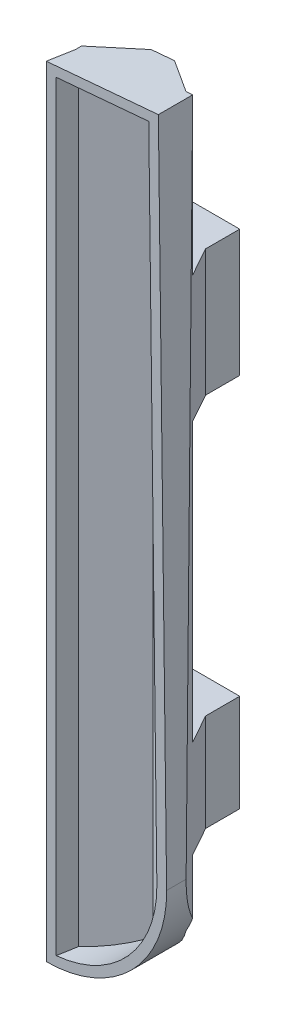
SolidWorks part; units mm, degrees
ref_plane "Front Plane" through (0, 0, 0) normal (0, 0, 1) x (1, 0, 0)
ref_plane "Top Plane" through (0, 0, 0) normal (0, 1, 0) x (1, 0, 0)
ref_plane "Right Plane" through (0, 0, 0) normal (1, 0, 0) x (0, 0, -1)
sketch "Sketch1" plane through (0, 0, 0) normal (0, 0, 1) x (1, 0, 0)
  line L0 (0, 0) -> (0, 160)
  line L1 (0, 160) -> (23, 162.0122)
  line L2 (23, 162.0122) -> (24.693, 25)
  line L3 (0, 0) -> (-10, 0) construction
  arc A0 (24.693, 25) -> (0, 0) centre (0, 24.6949) cw
  point P6 (24.0103, 50.0035)
  point P8 (24.6946, 162.8435)
  dimension "D1" = 25
  dimension "D2" = 10
  dimension "D3" = 23
  dimension "D4" = 160
  dimension "D5" = 95
extrude "Front shape block" add sketch "Sketch1" against normal blind 20
sketch "Sketch2" plane through (0, 0, 0) normal (0, 1, 0) x (1, 0, 0)
  line L0 (0, 0) -> (1, 5)
  line L1 (1, 5) -> (1, 20)
  line L2 (23, 20) -> (0, 20) construction
  line L3 (1, 20) -> (0, 20)
  line L4 (19.693, 13) -> (24.693, 4)
  line L5 (24.693, 20) -> (24.693, 0) construction
  line L6 (0, 20) -> (0, 0)
  line L8 (24.693, 20) -> (24.693, 4) construction
  line L9 (19.693, 13) -> (19.693, 20)
  line L10 (19.693, 20) -> (24.693, 20)
  line L11 (24.693, 20) -> (25.693, 20)
  line L12 (25.693, 20) -> (25.693, 4)
  line L13 (25.693, 4) -> (24.693, 4)
  dimension "D1" = 1
  dimension "D2" = 5
  dimension "D3" = 4
  dimension "D4" = 5
  dimension "D5" = 9
  dimension "D6" = 1
extrude "Vertical shape cut" cut sketch "Sketch2" along normal through all
sketch "Sketch3" plane through (0, 0, -20) normal (0, 0, -1) x (-1, 0, 0)
  line L0 (0, 160) -> (0, 0) construction
  line L1 (-23, 162.0122) -> (0, 162.0122)
  line L3 (-23.3954, 130.0122) -> (0, 130.0122)
  line L4 (0, 162.0122) -> (0, 130.0122)
  line L5 (-24.693, 25) -> (-23, 162.0122) construction
  line L6 (-23.3954, 130.0122) -> (-23, 162.0122)
  line L7 (-23.7167, 104.0122) -> (-24.421, 47.0122)
  line L8 (-24.421, 47.0122) -> (0, 47.0122)
  line L9 (0, 47.0122) -> (0, 104.0122)
  line L10 (0, 104.0122) -> (-23.7167, 104.0122)
  line L11 (0, 0) -> (0, 27.0122)
  line L12 (0, 27.0122) -> (-24.6681, 27.0122)
  line L13 (-24.6681, 27.0122) -> (-24.693, 25)
  arc A0 (-24.693, 25) -> (0, 0) centre (0, 24.6949) ccw construction
  arc A1 (-24.693, 25) -> (0, 0) centre (0, 24.6949) ccw
  dimension "D1" = 32
  dimension "D2" = 58
  dimension "D3" = 115
  dimension "D4" = 135
extrude "Internal tab clearance cut" cut sketch "Sketch3" against normal offset from surface (8 mm away) 12 up to face at (13.229, 85.4634, 0)
shell "Shell" thickness 2 removed face at (13.229, 85.4634, 0)
sketch "Sketch4" plane through (0, 0, -10) normal (0, 0, 1) x (1, 0, 0)
  line L0 (19.0717, 45.0122) -> (3, 45.0122)
  line L1 (3, 45.0122) -> (3, 29.0122)
  line L2 (3, 29.0122) -> (19.0717, 29.0122)
  line L3 (19.0717, 29.0122) -> (19.0717, 45.0122)
  line L4 (19.0717, 128.0122) -> (3, 128.0122)
  line L5 (3, 128.0122) -> (3, 106.0122)
  line L6 (3, 106.0122) -> (19.0717, 106.0122)
  line L7 (19.0717, 106.0122) -> (19.0717, 128.0122)
extrude "Mount tab fill" add sketch "Sketch4" against normal up to next
ref_plane "Plane1" through (0, 158.2548, 0) normal (0, 1, 0) x (1, 0, 0)
sketch "Sketch5" plane through (19.7814, 158.2548, 0) normal (0, 1, 0) x (-1, 0, 0)
  line L14 (16.9748, -3.8351) -> (7.8647, -10)
  line L15 (16.7814, -4.802) -> (17.7418, 0) construction
  line L16 (0.7097, -10) -> (16.7814, -10) construction
  line L17 (7.8647, -10) -> (-1.2454, -3.8351)
  line L18 (-1.2454, -6.4809) -> (-1.2454, 0) construction
  line L19 (-1.2454, -3.8351) -> (-1.2454, -6.4809)
  line L20 (-1.2454, -6.4809) -> (0.7097, -10)
  line L21 (0.7097, -10) -> (7.8647, -10)
  line L22 (16.7814, -10) -> (16.7814, -4.802)
  line L23 (16.7814, -4.802) -> (16.9748, -3.8351)
  line L24 (7.8647, -10) -> (16.7814, -10)
  point P16 (16.5963, -10)
  dimension "D1" = 11
extrude "LED strip tray" add sketch "Sketch5" against normal up to surface and the other way up to surface contours L20 L21 L17 L19 | L14 L24 L22 L23 region at (5.9631, 158.2548, -7.9773) region at (17.6571, 158.2548, -7.8219) up to face at (14.5201, 12.4524, -4.3202) other way up to face at (11.5275, 159.0009, -5.2138)
sketch "Sketch6" plane through (21.0268, 0, 0) normal (1, 0, 0) x (0, 0, -1)
  line L4 (3.8351, 159.832) -> (3.8351, 16.1549)
  line L5 (3.8351, 16.1549) -> (6.4809, 16.1549)
  line L6 (6.4809, 16.1549) -> (6.4809, 159.832)
  line L7 (6.4809, 159.832) -> (3.8351, 159.832)
  line L8 (3.8351, 159.832) -> (3.8351, 16.1549)
  line L9 (3.8351, 16.1549) -> (6.4809, 16.1549)
  line L10 (6.4809, 16.1549) -> (6.4809, 159.832)
  line L11 (6.4809, 159.832) -> (3.8351, 159.832)
  dimension "D1" = 0
extrude "Tray gap fill" add sketch "Sketch6" along normal up to next
sketch "Sketch7" plane through (0, 130.0122, 0) normal (0, 1, 0) x (1, 0, 0)
  line L0 (11.9167, 10) -> (21.0268, 3.8351) construction
  line L1 (2.8066, 3.8351) -> (11.9167, 10) construction
  line L2 (11.9167, 10) -> (21.0268, 3.8351) construction
  line L3 (2.8066, 3.8351) -> (11.9167, 10) construction
  line L4 (1, 6.2349) -> (9.5193, 12)
  line L7 (1, 12) -> (20.2486, 12) construction
  line L8 (1, 12) -> (1, 5) construction
  line L9 (14.3141, 12) -> (21.6327, 7.0474)
  line L10 (23, 7.0474) -> (21.6327, 7.0474)
  line L11 (23, 7.0474) -> (20.2486, 12)
  line L12 (20.2486, 12) -> (14.3141, 12)
  line L13 (9.5193, 12) -> (1, 12)
  line L14 (1, 12) -> (1, 6.2349)
  dimension "D1" = 3
  dimension "D2" = 3
extrude "Cut-Extrude4" cut sketch "Sketch7" along normal through all
sketch "Sketch8" plane through (0, 47.0122, 0) normal (0, 1, 0) x (1, 0, 0)
  line L3 (9.5193, 12) -> (1, 12)
  line L4 (14.3141, 12) -> (21.6327, 7.0474)
  line L5 (21.6327, 7.0474) -> (23, 7.0474)
  line L6 (23, 7.0474) -> (20.2486, 12)
  line L7 (20.2486, 12) -> (14.3141, 12)
  line L8 (14.3141, 12) -> (21.6327, 7.0474)
  line L9 (21.6327, 7.0474) -> (23, 7.0474)
  line L10 (23, 7.0474) -> (20.2486, 12)
  line L11 (20.2486, 12) -> (14.3141, 12)
  line L12 (1, 6.2349) -> (9.5193, 12)
  line L13 (1, 12) -> (1, 6.2349)
  line L14 (9.5193, 12) -> (1, 12)
  line L15 (1, 6.2349) -> (9.5193, 12)
  line L16 (1, 12) -> (1, 6.2349)
  dimension "D1" = 0
  dimension "D2" = 0
extrude "Cut-Extrude5" cut sketch "Sketch8" along normal up to surface (57 mm away) up to face at (12.3269, 104.0122, -15.4)
sketch "Sketch9" plane through (0, 27.0122, 0) normal (0, -1, 0) x (1, 0, 0)
  line L3 (1, -12) -> (9.5193, -12)
  line L4 (21.6327, -7.0474) -> (14.3141, -12)
  line L5 (23, -7.0474) -> (21.6327, -7.0474)
  line L6 (20.2486, -12) -> (23, -7.0474)
  line L7 (14.3141, -12) -> (20.2486, -12)
  line L8 (21.6327, -7.0474) -> (14.3141, -12)
  line L9 (23, -7.0474) -> (21.6327, -7.0474)
  line L10 (20.2486, -12) -> (23, -7.0474)
  line L11 (14.3141, -12) -> (20.2486, -12)
  line L12 (9.5193, -12) -> (1, -6.2349)
  line L13 (1, -6.2349) -> (1, -12)
  line L14 (1, -12) -> (9.5193, -12)
  line L15 (9.5193, -12) -> (1, -6.2349)
  line L16 (1, -6.2349) -> (1, -12)
  dimension "D1" = 0
  dimension "D2" = 0
extrude "Cut-Extrude6" cut sketch "Sketch9" along normal through all
